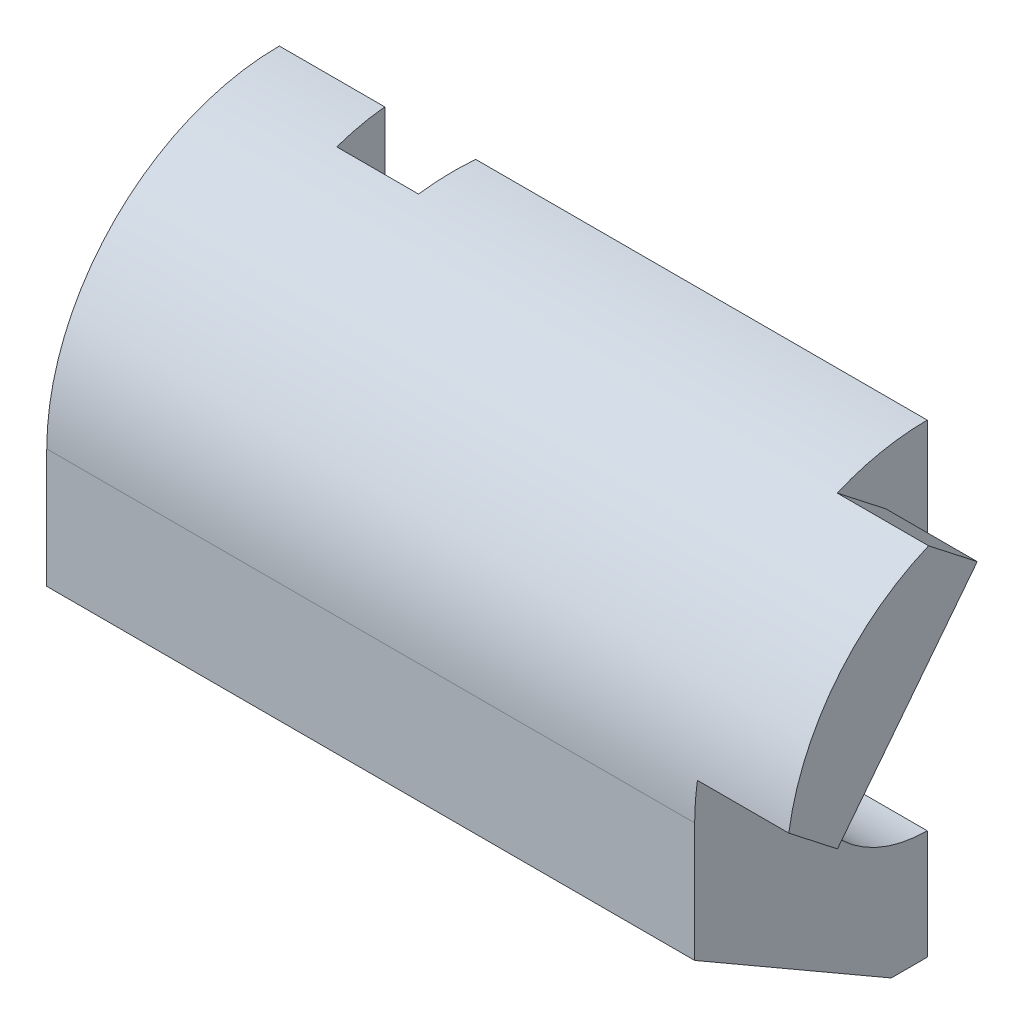
SolidWorks part; units mm, degrees
material "1060 Alloy"
ref_plane "Front Plane" through (0, 0, 0) normal (0, 0, 1) x (1, 0, 0)
ref_plane "Top Plane" through (0, 0, 0) normal (0, 1, 0) x (1, 0, 0)
ref_plane "Right Plane" through (0, 0, 0) normal (1, 0, 0) x (0, 0, -1)
sketch "Sketch1" plane through (0, 0, 0) normal (1, 0, 0) x (0, 0, -1)
  line L0 (0, 0) -> (-13, 0)
  line L1 (-13, 0) -> (-84, 40.9919)
  line L2 (-84, 40.9919) -> (-84, 84)
  line L3 (0, 0) -> (0, 55.425)
  line L4 (0, 168) -> (0, 112.575)
  arc A0 (0, 55.425) -> (0, 112.575) centre (0, 84) cw
  arc A1 (0, 168) -> (-84, 84) centre (0, 84) ccw
  point P6 (0, 0)
  dimension "D1" = 28.575
  dimension "D6" = 84
  dimension "D2" = 84
  dimension "D3" = 84
  dimension "D4" = 13
  dimension "D5" = 30
extrude "Boss-Extrude1" add sketch "Sketch1" along normal blind 234
sketch "Sketch2" plane through (234, 0, 0) normal (1, 0, 0) x (0, 0, -1)
  line L0 (0, 112.575) -> (0, 55.425) construction
  line L1 (0, 0) -> (0, 55.425) construction
  line L2 (0, 112.575) -> (0, 168) construction
  line L3 (0, 128.45) -> (0, 39.55)
  arc A0 (0, 39.55) -> (0, 128.45) centre (0, 84) cw
  dimension "D1" = 44.45
extrude "Cut-Extrude1" cut sketch "Sketch2" against normal blind 78
sketch "Sketch3" plane through (234, 0, 0) normal (1, 0, 0) x (0, 0, -1)
  line L0 (-83.0146, 96.8284) -> (-65.4307, 83.0903)
  line L1 (-65.4307, 83.0903) -> (-14.9464, 147.7072)
  line L2 (-14.9464, 147.7072) -> (-32.5304, 161.4453)
  line L3 (-13, 0) -> (0, 0) construction
  line L4 (0, 112.575) -> (0, 55.425) construction
  arc A0 (0, 168) -> (-84, 84) centre (0, 84) ccw construction
  arc A1 (-83.0146, 96.8284) -> (-32.5304, 161.4453) centre (0, 84) cw
  point P2 (0, 84)
  point P11 (-13.0105, 148.185)
  point P15 (-13.666, 147.346)
  dimension "D1" = 82
  dimension "D2" = 51
  dimension "D3" = 38
extrude "Boss-Extrude2" add sketch "Sketch3" along normal blind 33
sketch "Sketch4" plane through (0, 0, 0) normal (0, 0, -1) x (-1, 0, 0)
  line L0 (0, 26) -> (-117, 26) construction
  line L1 (0, 0) -> (0, 55.425) construction
  line L2 (0, 15) -> (-117, 15)
  line L3 (0, 37) -> (-117, 37)
  line L4 (-234, 0) -> (0, 0) construction
  arc A0 (0, 15) -> (0, 37) centre (0, 26) ccw
  arc A1 (-117, 37) -> (-117, 15) centre (-117, 26) ccw
  point P4 (-58.5, 26)
  dimension "D2" = 11
  dimension "D1" = 117
  dimension "D3" = 26
extrude "Cut-Extrude2" cut sketch "Sketch4" against normal blind 13
sketch "Sketch6" plane through (0, 0, 0) normal (0, 0, -1) x (-1, 0, 0)
  line L0 (-71, 168) -> (-71, 83.5301)
  line L1 (-234, 168) -> (0, 168) construction
  line L2 (-71, 83.5301) -> (-38, 83.5301)
  line L3 (-38, 83.5301) -> (-38, 168)
  line L4 (-38, 168) -> (-71, 168)
  line L5 (0, 112.575) -> (0, 168) construction
  dimension "D1" = 33
  dimension "D2" = 38
extrude "Cut-Extrude3" cut sketch "Sketch6" against normal blind 19
chamfer "Chamfer2" distance 20 angle 5 2 edges at (38, 135.5831, 19) (71, 135.5831, 19) first distance on face at (38, 138.5076, 9.6818) first distance on face at (71, 138.5076, 9.6818)
equation "\"A\" = 234"
equation "\"B\" = 117"
equation "\"C\" = 84"
equation "\"D2@Sketch1\"=\"C\""
equation "\"D3@Sketch1\"=\"C\""
equation "\"D6@Sketch1\"=\"C\""
equation "\"D1@Boss-Extrude1\"=\"A\""
equation "\"D1@Sketch4\"=\"B\""
equation "\"D\"= 5"
equation "\"D2@Chamfer2\"=\"D\""
